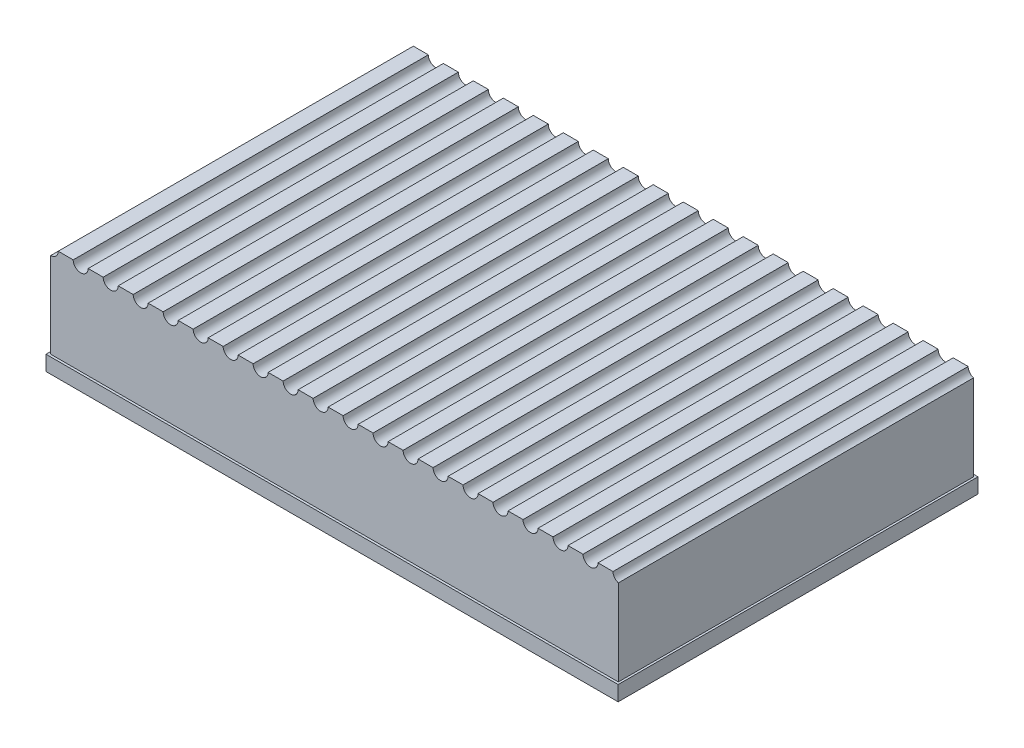
SolidWorks part; units mm, degrees
ref_plane "Front Plane" through (0, 0, 0) normal (0, 0, 1) x (1, 0, 0)
ref_plane "Top Plane" through (0, 0, 0) normal (0, 1, 0) x (1, 0, 0)
ref_plane "Right Plane" through (0, 0, 0) normal (1, 0, 0) x (0, 0, -1)
sketch "Sketch1" plane through (0, 0, 0) normal (0, 1, 0) x (1, 0, 0)
  line L1 (0, 0) -> (-121.1453, 0)
  line L2 (0, 0) -> (0, 76.2)
  line L3 (0, 76.2) -> (-121.1453, 76.2)
  line L4 (-121.1453, 0) -> (-121.1453, 76.2)
  dimension "D1" = 121.1453
  dimension "D2" = 76.2
extrude "Boss-Extrude1" add sketch "Sketch1" along normal blind 3.175
sketch "Sketch3" plane through (0, 3.175, 0) normal (0, 1, 0) x (1, 0, 0)
  line L0 (-0.4551, 75.7) -> (-120.65, 75.7)
  line L1 (-120.65, 75.7) -> (-120.65, 0.5)
  line L2 (-120.65, 0.5) -> (-0.4551, 0.5)
  line L3 (-0.4551, 0.5) -> (-0.4551, 14.0347)
  line L4 (-0.4551, 14.0347) -> (-0.4551, 75.7)
extrude "Boss-Extrude4" add sketch "Sketch3" along normal blind 19.685
sketch "Sketch4" plane through (0, 0, -0.5) normal (0, 0, 1) x (1, 0, 0)
  circle A0 centre (-120.65, 22.86) radius 1.5875
  circle A1 centre (-114.3, 22.86) radius 1.5875
  circle A2 centre (-107.95, 22.86) radius 1.5875
  circle A3 centre (-101.6, 22.86) radius 1.5875
  circle A4 centre (-95.25, 22.86) radius 1.5875
  circle A5 centre (-88.9, 22.86) radius 1.5875
  circle A6 centre (-82.55, 22.86) radius 1.5875
  circle A7 centre (-76.2, 22.86) radius 1.5875
  circle A8 centre (-69.85, 22.86) radius 1.5875
  circle A9 centre (-63.5, 22.86) radius 1.5875
  circle A10 centre (-57.15, 22.86) radius 1.5875
  circle A11 centre (-50.8, 22.86) radius 1.5875
  circle A12 centre (-44.45, 22.86) radius 1.5875
  circle A13 centre (-38.1, 22.86) radius 1.5875
  circle A14 centre (-31.75, 22.86) radius 1.5875
  circle A15 centre (-25.4, 22.86) radius 1.5875
  circle A16 centre (-19.05, 22.86) radius 1.5875
  circle A17 centre (-12.7, 22.86) radius 1.5875
  circle A18 centre (-6.35, 22.86) radius 1.5875
  circle A19 centre (0, 22.86) radius 1.5875
  circle A20 centre (6.35, 22.86) radius 1.5875
  dimension "D1" = 3.175
  dimension "D2" = 21
extrude "Cut-Extrude1" cut sketch "Sketch4" against normal through all
